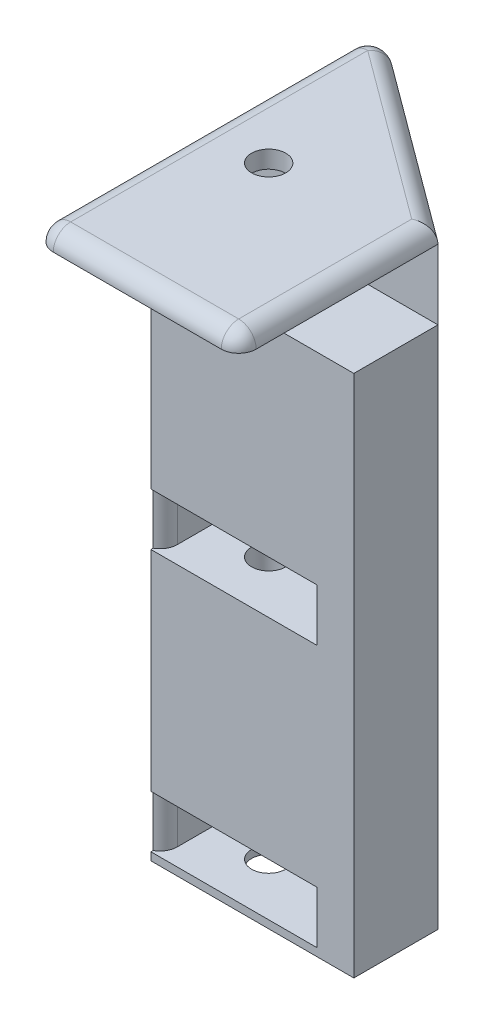
SolidWorks part; units mm, degrees
note: The reader was unsure of these and kept them because the rebuilt part matched: shared geometry of "Sketch1<3>".
material "PLA/ABS"
ref_plane "Front Plane" through (0, 0, 0) normal (0, 0, 1) x (1, 0, 0)
ref_plane "Top Plane" through (0, 0, 0) normal (0, 1, 0) x (1, 0, 0)
ref_plane "Right Plane" through (0, 0, 0) normal (1, 0, 0) x (0, 0, -1)
other "Bounding Box"
ref_plane "Default Plane" through (-8.9266, -12.7485, 0) normal (-0.1736, 0.9848, 0) x (0.9848, 0.1736, 0)
sketch "Sketch1" plane through (0, 0, 0) normal (0, 1, 0) x (1, 0, 0)
  line B0 (-13.2357, 21.8055) -> (-13.2357, -16.2945)
  line B1 (-13.2357, -16.2945) -> (16.2964, -16.2945)
  line B2 (16.2964, -16.2945) -> (16.2964, 0)
  line B3 (16.2964, 0) -> (-13.2357, 21.8055)
  line B4 (16.2964, 0) -> (-13.2357, 0)
sketch_block_instance "Inter mount mount-1"
sketch_block "Inter mount mount" parameters "D1"=38.1
extrude "Boss-Extrude1" add sketch "Sketch1" along normal blind 6.35 contours B4 B3 B0 | B2 B4 B0 B1
extrude "Boss-Extrude2" add sketch "Sketch1<3>" against normal blind 82.55 contours B4 B3 B0
sketch "Sketch1<3>" plane through (0, 0, 0) normal (0, 1, 0) x (1, 0, 0) same geometry as "Sketch1"
sketch "Sketch2" plane through (0, 0, 0) normal (0, -1, 0) x (-1, 0, 0)
  line L0 (13.2357, 0) -> (-16.2964, 0)
  line L5 (13.2357, 0) -> (13.2357, -16.2945)
  line L6 (-16.2964, 0) -> (-16.2964, -16.2945)
  line L7 (13.2357, -16.2945) -> (-16.2964, -16.2945)
  line L8 (13.2357, -16.2945) -> (-16.2964, -16.2945) construction
extrude "Cut-Extrude1" cut sketch "Sketch2" against normal blind 3.175
sketch "Sketch4" plane through (0, 6.35, 0) normal (0, 1, 0) x (1, 0, 0)
  line L0 (16.2964, -16.2945) -> (16.2964, 0) construction
  line L1 (-13.2357, -16.2945) -> (16.2964, -16.2945)
  line L2 (-13.2357, -16.2945) -> (-13.2357, -28.9945)
  line L3 (-13.2357, -28.9945) -> (16.2964, -28.9945)
  line L4 (16.2964, -16.2945) -> (16.2964, -28.9945)
  dimension "D1" = 12.7
extrude "Boss-Extrude3" add sketch "Sketch4" against normal up to surface (3.175 mm away) up to face at (1.5304, 3.175, 8.1472)
sketch3d "3DSketch1" plane through (0, 0, 0) normal (0, 0, 1) x (1, 0, 0)
  dimension "D1" = 3.175
sketch "Sketch7" plane through (3.8639, 0, -5.2331) normal (0.594, 0, -0.8045) x (-0.8045, 0, -0.594)
  line L0 (-13.11, -82.55) -> (-13.11, 3.175) construction
  line L1 (-13.11, -73.787) -> (23.6, -73.787)
  line L2 (-13.11, -73.787) -> (-13.11, -81.407)
  line L3 (-13.11, -81.407) -> (23.6, -81.407)
  line L4 (23.6, -73.787) -> (23.6, -81.407)
  line L5 (23.6, 6.35) -> (23.6, -82.55) construction
  line L6 (-13.11, -82.55) -> (23.6, -82.55) construction
  dimension "D1" = 1.143
  dimension "D2" = 7.62
extrude "Cut-Extrude4" cut sketch "Sketch7" against normal blind 13.589 contours L2 L1 L4 L3
sketch "Sketch8" plane through (3.8639, 0, -5.2331) normal (0.594, 0, -0.8045) x (-0.8045, 0, -0.594)
  line L0 (-13.11, -82.55) -> (-13.11, 3.175) construction
  line L1 (-13.11, -43.307) -> (23.6, -43.307)
  line L2 (-13.11, -43.307) -> (-13.11, -35.687)
  line L3 (-13.11, -35.687) -> (23.6, -35.687)
  line L4 (23.6, -43.307) -> (23.6, -35.687)
  line L5 (23.6, 6.35) -> (23.6, -82.55) construction
  line L7 (-8.81, -73.787) -> (9.5942, -73.787) construction
  dimension "D1" = 30.48
  dimension "D2" = 7.62
extrude "Cut-Extrude5" cut sketch "Sketch8" against normal blind 13.589
sketch "Sketch9" plane through (0, 0, 0) normal (0, 0, 1) x (1, 0, 0)
  line L1 (-13.2357, -82.55) -> (16.2964, -82.55)
  line L2 (-13.2357, -82.55) -> (-13.2357, 3.175)
  line L3 (-13.2357, 3.175) -> (16.2964, 3.175)
  line L4 (16.2964, -82.55) -> (16.2964, 3.175)
  line L5 (-11.9261, -43.307) -> (10.9513, -43.307)
  line L6 (-11.9261, -43.307) -> (-11.9261, -35.687)
  line L7 (-11.9261, -35.687) -> (10.9513, -35.687)
  line L8 (10.9513, -43.307) -> (10.9513, -35.687)
  line L9 (-11.9261, -81.407) -> (10.9513, -81.407)
  line L10 (-11.9261, -81.407) -> (-11.9261, -73.787)
  line L11 (-11.9261, -73.787) -> (10.9513, -73.787)
  line L12 (10.9513, -81.407) -> (10.9513, -73.787)
  line L13 (-13.2357, 3.175) -> (16.2964, 3.175)
  line L14 (-13.2357, 3.175) -> (-13.2357, -6.35)
  line L15 (-13.2357, -6.35) -> (16.2964, -6.35)
  line L16 (16.2964, 3.175) -> (16.2964, -6.35)
  line M9 (10.9513, -43.307) -> (-11.9261, -43.307)
  line M10 (-11.9261, -43.307) -> (-11.9261, -35.687)
  line M11 (-11.9261, -35.687) -> (10.9513, -35.687)
  line M12 (10.9513, -35.687) -> (10.9513, -43.307)
  line M13 (10.9513, -81.407) -> (-11.9261, -81.407)
  line M14 (-11.9261, -81.407) -> (-11.9261, -73.787)
  line M15 (-11.9261, -73.787) -> (10.9513, -73.787)
  line M16 (10.9513, -73.787) -> (10.9513, -81.407)
  line M17 (16.2964, -82.55) -> (16.2964, 3.175)
  line M20 (-13.2357, -82.55) -> (16.2964, -82.55)
  dimension "D1" = 9.525
extrude "Boss-Extrude5" add sketch "Sketch9" along normal blind 12.2428 contours L15 L2 M20 M17 M16 M13 M14 M15 M12 M9 M10 M11
sketch "Sketch10" plane through (0, -82.55, 0) normal (0, -1, 0) x (-1, 0, 0)
  line L0 (13.2357, 21.8055) -> (13.2357, -12.2428) construction
  line L1 (13.2357, -12.2428) -> (-16.2964, -12.2428) construction
  circle A0 centre (3.7107, -4.6228) radius 2.4892
  dimension "D1" = 4.9784
  dimension "D3" = 7.62
  dimension "D2" = 9.525
extrude "Cut-Extrude6" cut sketch "Sketch10" against normal through all both and the other way through all
fillet "Fillet2" radius 2.54 7 edges at (-13.2357, -38.1, -21.8055) (-11.9261, -77.597, 0) (-11.9261, -77.597, 12.2428) (-11.9261, -39.497, 12.2428) (-11.9261, -39.497, 0) (-13.2357, 4.7625, 28.9945) (16.2964, 4.7625, 28.9945)
fillet "Fillet3" radius 2.54 7 edges at (16.2964, 6.35, 13.2272) (15.5525, 6.35, 28.2505) (1.5304, 6.35, 28.9945) (-12.4917, 6.35, 28.2505) (-13.2357, 6.35, 4.8409) (-11.8401, 6.35, -19.0403) (3.5547, 6.35, -9.408)
mirror "Mirror1" [suppressed]
delete or keep bodies "Body-Delete/Keep 1" [suppressed] type delete bodies bodies 114
sketch "Sketch11" plane through (5.7498, 0, -7.7872) normal (0.594, 0, -0.8045) x (-0.8045, 0, -0.594)
  circle A0 centre (-11.0457, -62.23) radius 1.5875
  circle A1 centre (1.6543, -62.23) radius 1.5875
  circle A2 centre (14.3543, -62.23) radius 1.5875
  circle A3 centre (-11.0457, -36.83) radius 1.5875
  circle A4 centre (1.6543, -36.83) radius 1.5875
  circle A5 centre (14.3543, -36.83) radius 1.5875
  circle A6 centre (-11.0457, -11.43) radius 1.5875
  circle A7 centre (1.6543, -11.43) radius 1.5875
  circle A8 centre (14.3543, -11.43) radius 1.5875
  dimension "D1" = 3
  dimension "D2" = 3
extrude "Cut-Extrude7" cut sketch "Sketch11" against normal blind 6.35 and the other way blind 2.54
sketch "Sketch12" plane through (16.2964, 0, 0) normal (1, 0, 0) x (0, 0, -1)
  line L1 (0, 3.81) -> (-28.9945, 3.81)
  line L2 (0, 3.81) -> (0, 3.175)
  line L3 (0, 3.175) -> (-28.9945, 3.175)
  line L4 (-28.9945, 3.81) -> (-28.9945, 3.175)
extrude "Cut-Extrude8" cut sketch "Sketch12" against normal through all both and the other way through all
